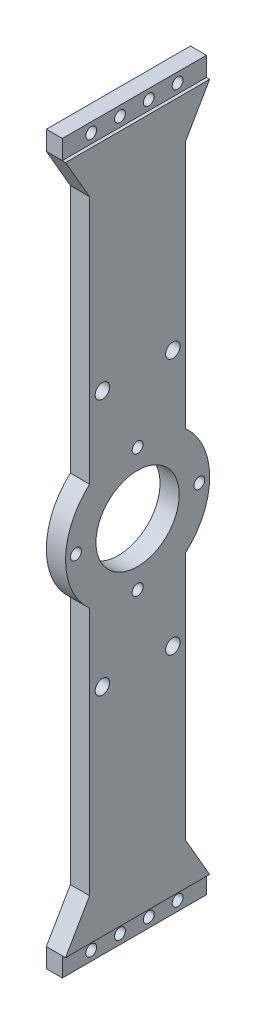
SolidWorks part; units mm, degrees
material "Сплав 2024"
ref_plane "Спереди" through (0, 0, 0) normal (0, 0, 1) x (1, 0, 0)
ref_plane "Сверху" through (0, 0, 0) normal (0, 1, 0) x (1, 0, 0)
ref_plane "Справа" through (0, 0, 0) normal (1, 0, 0) x (0, 0, -1)
sketch "Эскиз1" plane through (0, 0, 0) normal (0, 1, 0) x (1, 0, 0)
  line L1 (0, 0) -> (6, 0)
  line L2 (0, 0) -> (0, -30)
  line L3 (0, -30) -> (6, -30)
  line L4 (6, 0) -> (6, -30)
  dimension "D1" = 6
  dimension "D2" = 30
extrude "Бобышка-Вытянуть1" add sketch "Эскиз1" along normal blind 227
sketch "Эскиз2" plane through (0, 0, 0) normal (-1, 0, 0) x (0, 0, 1)
  line L0 (30, 113.5) -> (0, 113.5) construction
  line L1 (30, 227) -> (30, 0) construction
  line L2 (0, 227) -> (0, 0) construction
  line L3 (15, 227) -> (15, 0) construction
  line L4 (0, 227) -> (30, 227) construction
  line L5 (0, 0) -> (30, 0) construction
  circle A0 centre (15, 113.5) radius 22.5
  dimension "D1" = 45
extrude "Бобышка-Вытянуть2" add sketch "Эскиз2" against normal up to surface (6 mm away) up to face at (6, 113.5, 15)
sketch "Эскиз3" plane through (0, 0, 0) normal (-1, 0, 0) x (0, 0, 1)
  circle A0 centre (15, 113.5) radius 13
  dimension "D1" = 26
extrude "Вырез-Вытянуть1" cut sketch "Эскиз3" against normal through all
sketch "Эскиз4" plane through (6, 0, 0) normal (-1, 0, 0) x (0, 0, 1)
  line L0 (15, 136) -> (15, 91) construction
  line L1 (15, 227) -> (15, 0) construction
  line L2 (37.5, 113.5) -> (-7.5, 113.5) construction
  circle A0 centre (15, 113.5) radius 19.25 construction
  circle A1 centre (15, 113.5) radius 22.5 construction
  dimension "D1" = 38.5
hole_wizard "Отверстие с зазором M32" positions "Эскиз6" profile "Эскиз5" hole size "M3" standard "Ansi Metric" end condition up to next
sketch "Эскиз6" plane through (6, -25.0247, 7.2629) normal (-1, 0, 0) x (0, 0, 1)
  line L0 (7.7371, 161.0247) -> (7.7371, 116.0247) construction
  line L1 (30.2371, 138.5247) -> (-14.7629, 138.5247) construction
  circle A0 centre (7.7371, 138.5247) radius 19.25 construction
  point P0 (7.7371, 157.7747)
  point P6 (-11.5129, 138.5247)
  point P10 (7.7371, 119.2747)
  point P12 (26.9871, 138.5247)
sketch "Эскиз5" plane through (6, 132.75, 15) normal (0, 1, 0) x (0, 0, -1)
  line L0 (0, 0) -> (0, 6)
  line L1 (0, 6) -> (1.7, 6)
  line L2 (1.7, 6) -> (1.7, 0)
  line L5 (1.7, 0) -> (0, 0)
  line L11 (0, -6.35) -> (0, 107.95) construction
  dimension "Диаметр сквозного отверстия" = 3.4
  dimension "Глубина сквозного отверстия" = 6
sketch "Эскиз8" plane through (6, 0, 0) normal (1, 0, 0) x (0, 0, -1)
  line L0 (-15, 227) -> (-15, 0) construction
  line L1 (-30, 227) -> (0, 227) construction
  line L2 (-30, 0) -> (0, 0) construction
  line L3 (19.447, 113.5) -> (-49.447, 113.5) construction
  line L4 (0, 227) -> (0, 130.2705) construction
  line L5 (-26, 153.5) -> (-4, 153.5) construction
  line L6 (-26, 153.5) -> (-26, 73.5) construction
  line L7 (-26, 73.5) -> (-4, 73.5) construction
  line L8 (-4, 153.5) -> (-4, 73.5) construction
  line L9 (-26, 153.5) -> (-4, 73.5) construction
  line L10 (-26, 73.5) -> (-4, 153.5) construction
  point P8 (-15, 113.5)
  point P9 (-15, 113.5)
  dimension "D1" = 4
  dimension "D2" = 80
hole_wizard "Отверстие с зазором M41" positions "Эскиз10" profile "Эскиз9" hole size "M4" standard "Ansi Metric" end condition through all
sketch "Эскиз10" plane through (6, 0, 0) normal (1, 0, 0) x (0, 0, -1)
  point P0 (-26, 153.5)
  point P3 (-4, 153.5)
  point P6 (-4, 73.5)
  point P9 (-26, 73.5)
sketch "Эскиз9" plane through (6, 153.5, 26) normal (0, 1, 0) x (0, 0, -1)
  line L0 (0, 0) -> (0, 6)
  line L1 (0, 6) -> (2.25, 6)
  line L2 (2.25, 6) -> (2.25, 0)
  line L5 (2.25, 0) -> (0, 0)
  line L11 (0, -6.35) -> (0, 107.95) construction
  dimension "Диаметр сквозного отверстия" = 4.5
  dimension "Глубина сквозного отверстия" = 6
sketch "Эскиз11" plane through (6, 0, 0) normal (1, 0, 0) x (0, 0, -1)
  line L0 (-15, 227) -> (-15, 0) construction
  line L1 (-30, 227) -> (0, 227) construction
  line L2 (-30, 0) -> (0, 0) construction
  line L3 (-37.5, 221) -> (-30, 208.0096)
  line L4 (-37.5, 221) -> (7.5, 221) construction
  line L5 (-37.5, 221) -> (-37.5, 227)
  line L6 (-37.5, 227) -> (7.5, 227)
  line L7 (7.5, 221) -> (7.5, 227)
  line L8 (-37.5, 221) -> (7.5, 227) construction
  line L9 (-37.5, 227) -> (7.5, 221) construction
  line L10 (-30, 227) -> (-30, 130.2705) construction
  line L11 (-30, 208.0096) -> (0, 208.0096)
  line L12 (0, 227) -> (0, 130.2705) construction
  line L13 (0, 208.0096) -> (7.5, 221)
  line L14 (-37.5, 224) -> (7.5, 224) construction
  line L15 (-28.5, 227) -> (-28.5, 221) construction
  line L16 (-19.5, 227) -> (-19.5, 221) construction
  line L17 (-10.5, 227) -> (-10.5, 221) construction
  line L18 (-1.5, 227) -> (-1.5, 221) construction
  line L19 (-15, 113.5) -> (-5.455, 113.5) construction
  line L20 (-1.5, 0) -> (-1.5, 6) construction
  line L21 (-10.5, 0) -> (-10.5, 6) construction
  line L22 (-19.5, 0) -> (-19.5, 6) construction
  line L23 (-28.5, 0) -> (-28.5, 6) construction
  line L24 (-37.5, 3) -> (7.5, 3) construction
  line L25 (-37.5, 0) -> (7.5, 6) construction
  line L26 (-37.5, 6) -> (7.5, 0) construction
  line L27 (-37.5, 6) -> (7.5, 6) construction
  line L28 (0, 18.9904) -> (7.5, 6)
  line L29 (-30, 18.9904) -> (0, 18.9904)
  line L30 (7.5, 6) -> (7.5, 0)
  line L31 (-37.5, 0) -> (7.5, 0)
  line L32 (-37.5, 6) -> (-37.5, 0)
  line L33 (-37.5, 6) -> (-30, 18.9904)
  point P6 (-15, 224)
  point P45 (-15, 3)
  dimension "D1" = 6
  dimension "D2" = 45
  dimension "D3" = 120
  dimension "D4" = 9
  dimension "D5" = 9
  dimension "D6" = 9
  dimension "D7" = 9
extrude "Бобышка-Вытянуть3" add sketch "Эскиз11" against normal up to surface (6 mm away) up to face at (0, 153.5, 23.75)
hole_wizard "Отверстие с зазором M31" positions "Эскиз13" profile "Эскиз12" hole size "M3" standard "Ansi Metric" end condition through all
sketch "Эскиз13" plane through (6, 0, 0) normal (1, 0, 0) x (0, 0, -1)
  line L0 (-28.5, 227) -> (-28.5, 221) construction
  line L1 (-19.5, 227) -> (-19.5, 221) construction
  line L2 (-10.5, 227) -> (-10.5, 221) construction
  line L3 (-1.5, 227) -> (-1.5, 221) construction
  line L4 (-28.5, 0) -> (-28.5, 6) construction
  line L5 (-19.5, 0) -> (-19.5, 6) construction
  line L6 (-10.5, 0) -> (-10.5, 6) construction
  line L7 (-1.5, 0) -> (-1.5, 6) construction
  point P0 (-28.5, 224)
  point P4 (-19.5, 224)
  point P8 (-10.5, 224)
  point P12 (-1.5, 224)
  point P16 (-28.5, 3)
  point P20 (-19.5, 3)
  point P24 (-10.5, 3)
  point P28 (-1.5, 3)
sketch "Эскиз12" plane through (6, 224, 28.5) normal (0, 1, 0) x (0, 0, -1)
  line L0 (0, 0) -> (0, 6)
  line L1 (0, 6) -> (1.7, 6)
  line L2 (1.7, 6) -> (1.7, 0)
  line L5 (1.7, 0) -> (0, 0)
  line L11 (0, -6.35) -> (0, 107.95) construction
  dimension "Диаметр сквозного отверстия" = 3.4
  dimension "Глубина сквозного отверстия" = 6
sketch "Эскиз14" plane through (6, 0, 0) normal (1, 0, 0) x (0, 0, -1)
  line L1 (-37.5, 227) -> (7.5, 227)
  line L2 (-37.5, 227) -> (-37.5, 221)
  line L3 (-37.5, 221) -> (7.5, 221)
  line L4 (7.5, 227) -> (7.5, 221)
  line L5 (-37.5, 0) -> (7.5, 0)
  line L6 (-37.5, 0) -> (-37.5, 6)
  line L7 (-37.5, 6) -> (7.5, 6)
  line L8 (7.5, 0) -> (7.5, 6)
extrude "Вырез-Вытянуть2" cut sketch "Эскиз14" against normal blind 1
equation "\"D4@Эскиз11\"=\"D2@Эскиз11\"/5"
equation "\"D5@Эскиз11\"=\"D4@Эскиз11\""
equation "\"D6@Эскиз11\"=\"D4@Эскиз11\""
equation "\"D7@Эскиз11\"=\"D4@Эскиз11\""
